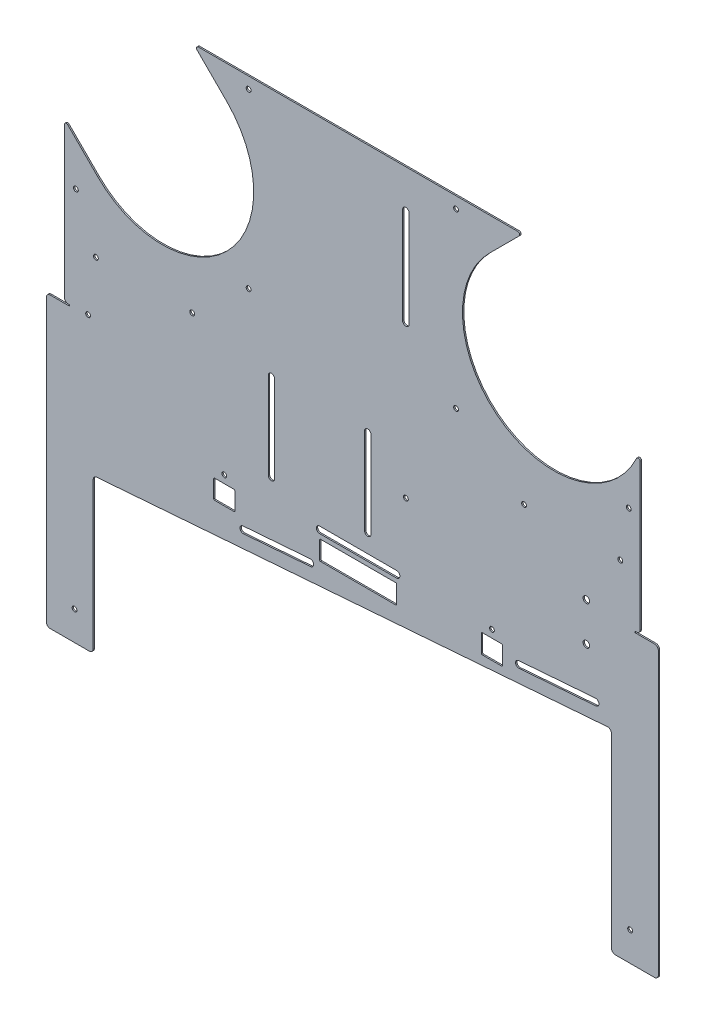
SolidWorks part; units mm, degrees
ref_plane "Front Plane" through (0, 0, 0) normal (0, 0, 1) x (1, 0, 0)
ref_plane "Top Plane" through (0, 0, 0) normal (0, 1, 0) x (1, 0, 0)
ref_plane "Right Plane" through (0, 0, 0) normal (1, 0, 0) x (0, 0, -1)
sketch "Model" plane through (0, 0, 0) normal (0, 0, 1) x (1, 0, 0)
  line L0 (179, 130) -> (179, 180)
  line L1 (175.6, 180) -> (175.6, 130)
  line L2 (155.85, 70.5824) -> (155.85, 25.5824)
  line L3 (159.15, 25.5824) -> (159.15, 70.5824)
  line L4 (109.15, 25.5824) -> (109.15, 70.5824)
  line L5 (105.85, 70.5824) -> (105.85, 25.5824)
  line L6 (172.5, 16.0516) -> (132.5, 16.0516)
  line L7 (132.5, 12.6516) -> (172.5, 12.6516)
  line L8 (275.6995, 10.2875) -> (235.8173, 7.2196)
  line L9 (275.9603, 6.8975) -> (236.0781, 3.8296)
  line L10 (77.5, 0.8516) -> (77.5, 9.8516)
  line L11 (78, 10.3516) -> (88, 10.3516)
  line L12 (88.5, 9.8516) -> (88.5, 0.8516)
  line L13 (78, 0.3516) -> (88, 0.3516)
  line L14 (216.5, 9.8516) -> (216.5, 0.8516)
  line L15 (217, 10.3516) -> (227, 10.3516)
  line L16 (227.5, 0.8516) -> (227.5, 9.8516)
  line L17 (217, 0.3516) -> (227, 0.3516)
  line L18 (132.5, 9.8516) -> (132.5, 0.8516)
  line L19 (133, 10.3516) -> (172, 10.3516)
  line L20 (172.5, 9.8516) -> (172.5, 0.8516)
  line L21 (133, 0.3516) -> (172, 0.3516)
  line L22 (127.8753, -4.4937) -> (92.9784, -7.178)
  line L23 (127.6145, -1.1037) -> (92.7176, -3.788)
  line L24 (0, 130.4106) -> (0, 52.635)
  line L25 (2.6416, 50.635) -> (2, 50.635)
  line L26 (2.6416, 50) -> (2.6416, 50.635)
  line L27 (-7.4113, 50) -> (2.6416, 50)
  line L28 (-9.4113, -98) -> (-9.4113, 48)
  line L29 (-7.4113, -100) -> (12.9289, -100)
  line L30 (14.9289, -98) -> (14.9289, -21.8521)
  line L31 (16.7755, -19.858) -> (281.9178, 0.5376)
  line L32 (284.0711, -1.4565) -> (284.0711, -98)
  line L33 (286.0711, -100) -> (306.4113, -100)
  line L34 (308.4113, 48) -> (308.4113, -98)
  line L35 (296.3584, 50) -> (306.4113, 50)
  line L36 (296.3584, 50.635) -> (296.3584, 50)
  line L37 (297, 50.635) -> (296.3584, 50.635)
  line L38 (299, 52.635) -> (299, 128.3719)
  line L39 (220.6124, 182.7876) -> (236.1177, 198.2929)
  line L40 (235.4106, 200) -> (69.5894, 200)
  line L41 (84.3876, 182.7876) -> (68.8823, 198.2929)
  line L42 (1.7071, 131.1177) -> (17.2124, 115.6124)
  arc A0 (179, 180) -> (175.6, 180) centre (177.3, 180) ccw
  arc A1 (175.6, 130) -> (179, 130) centre (177.3, 130) ccw
  circle A2 centre (177.3, 51) radius 1.25
  circle A3 centre (12.3, 51) radius 1.25
  circle A4 centre (271, 32.2) radius 1.7
  circle A5 centre (271, 52.2) radius 1.7
  circle A6 centre (5.25, -84.9) radius 1.25
  circle A7 centre (293.75, -84.9) radius 1.25
  arc A8 (155.85, 25.5824) -> (159.15, 25.5824) centre (157.5, 25.5824) ccw
  arc A9 (159.15, 70.5824) -> (155.85, 70.5824) centre (157.5, 70.5824) ccw
  arc A10 (109.15, 70.5824) -> (105.85, 70.5824) centre (107.5, 70.5824) ccw
  arc A11 (105.85, 25.5824) -> (109.15, 25.5824) centre (107.5, 25.5824) ccw
  arc A12 (132.5, 16.0516) -> (132.5, 12.6516) centre (132.5, 14.3516) ccw
  arc A13 (172.5, 12.6516) -> (172.5, 16.0516) centre (172.5, 14.3516) ccw
  circle A14 centre (83, 14.3516) radius 1.25
  circle A15 centre (222, 14.3516) radius 1.25
  arc A16 (235.8173, 7.2196) -> (236.0781, 3.8296) centre (235.9477, 5.5246) ccw
  arc A17 (275.9603, 6.8975) -> (275.6995, 10.2875) centre (275.8299, 8.5925) ccw
  arc A18 (78, 10.3516) -> (77.5, 9.8516) centre (78, 9.8516) ccw
  arc A19 (88.5, 9.8516) -> (88, 10.3516) centre (88, 9.8516) ccw
  arc A20 (88, 0.3516) -> (88.5, 0.8516) centre (88, 0.8516) ccw
  arc A21 (77.5, 0.8516) -> (78, 0.3516) centre (78, 0.8516) ccw
  arc A22 (217, 10.3516) -> (216.5, 9.8516) centre (217, 9.8516) ccw
  arc A23 (227.5, 9.8516) -> (227, 10.3516) centre (227, 9.8516) ccw
  arc A24 (227, 0.3516) -> (227.5, 0.8516) centre (227, 0.8516) ccw
  arc A25 (216.5, 0.8516) -> (217, 0.3516) centre (217, 0.8516) ccw
  circle A26 centre (238.6616, 78.8319) radius 1.25
  circle A27 centre (16.3384, 78.8315) radius 1.25
  circle A28 centre (203.3563, 104.3563) radius 1.25
  circle A29 centre (95.6437, 104.3563) radius 1.25
  circle A30 centre (95.6437, 194.0437) radius 1.25
  circle A31 centre (5.9563, 104.3563) radius 1.25
  circle A32 centre (203.3563, 194.0437) radius 1.25
  circle A33 centre (293.0437, 104.3563) radius 1.25
  circle A34 centre (66.3384, 78.8315) radius 1.25
  circle A35 centre (288.6616, 78.8319) radius 1.25
  arc A36 (133, 10.3516) -> (132.5, 9.8516) centre (133, 9.8516) ccw
  arc A37 (172.5, 9.8516) -> (172, 10.3516) centre (172, 9.8516) ccw
  arc A38 (172, 0.3516) -> (172.5, 0.8516) centre (172, 0.8516) ccw
  arc A39 (132.5, 0.8516) -> (133, 0.3516) centre (133, 0.8516) ccw
  arc A40 (127.8753, -4.4937) -> (127.6145, -1.1037) centre (127.7449, -2.7987) ccw
  arc A41 (92.7176, -3.788) -> (92.9784, -7.178) centre (92.848, -5.483) ccw
  arc A42 (0, 52.635) -> (2, 50.635) centre (2, 52.635) ccw
  arc A43 (-7.4113, 50) -> (-9.4113, 48) centre (-7.4113, 48) ccw
  arc A44 (-9.4113, -98) -> (-7.4113, -100) centre (-7.4113, -98) ccw
  arc A45 (12.9289, -100) -> (14.9289, -98) centre (12.9289, -98) ccw
  arc A46 (16.7755, -19.858) -> (14.9289, -21.8521) centre (16.9289, -21.8521) ccw
  arc A47 (284.0711, -1.4565) -> (281.9178, 0.5376) centre (282.0711, -1.4565) ccw
  arc A48 (284.0711, -98) -> (286.0711, -100) centre (286.0711, -98) ccw
  arc A49 (306.4113, -100) -> (308.4113, -98) centre (306.4113, -98) ccw
  arc A50 (308.4113, 48) -> (306.4113, 50) centre (306.4113, 48) ccw
  arc A51 (297, 50.635) -> (299, 52.635) centre (297, 52.635) ccw
  arc A52 (299, 128.3719) -> (297.0969, 128.8013) centre (298, 128.3719) ccw
  arc A53 (220.6124, 182.7876) -> (297.0969, 128.8013) centre (254.2, 149.2) ccw
  arc A54 (236.1177, 198.2929) -> (235.4106, 200) centre (235.4106, 199) ccw
  arc A55 (69.5894, 200) -> (68.8823, 198.2929) centre (69.5894, 199) ccw
  arc A56 (17.2124, 115.6124) -> (84.3876, 182.7876) centre (50.8, 149.2) ccw
  arc A57 (1.7071, 131.1177) -> (0, 130.4106) centre (1, 130.4106) ccw
sheet metal parameters "Sheet-Metal1" thickness 0.7 parameters "D1"=0.7366
base flange "Base-Flange1" sketch "Model" thickness 0.7 reverse thickness direction no parameters "D1"=0.7366
flat pattern "Flat-Pattern1" [suppressed]
sketch "Bend-Lines1" plane through (0, 0, 0) normal (0, 1, 0) x (1, 0, 0)
sketch3d "Bounding-Box1" [suppressed]
  line L0 (11.4111, 147.3651, 0) -> (-306.4114, 147.365, 0) construction
  line L1 (11.4113, -152.6348, 0) -> (-306.4112, -152.635, 0) construction
  line L2 (11.4111, 147.3651, 0) -> (11.4113, -152.6348, 0) construction
  line L3 (-306.4114, 147.365, 0) -> (-306.4112, -152.635, 0) construction
